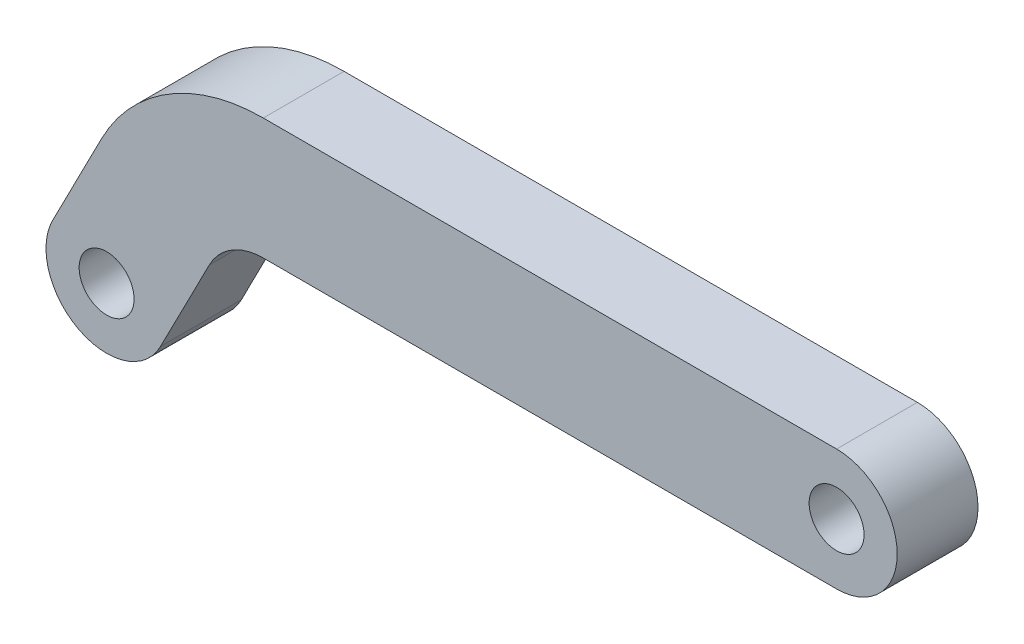
SolidWorks part; units mm, degrees
ref_plane "Front Plane" through (0, 0, 0) normal (0, 0, 1) x (1, 0, 0)
ref_plane "Top Plane" through (0, 0, 0) normal (0, 1, 0) x (1, 0, 0)
ref_plane "Right Plane" through (0, 0, 0) normal (1, 0, 0) x (0, 0, -1)
sketch "Sketch1" plane through (0, 0, 0) normal (0, 0, 1) x (1, 0, 0)
  line L0 (57.3602, 17.4078) -> (12.3107, 17.4078)
  line L2 (57.3602, 7.8828) -> (12.3107, 7.8828)
  line L3 (4.2363, -2.176) -> (8.0744, 5.2963)
  line L4 (-4.2363, 2.176) -> (-0.3983, 9.6482)
  line L5 (0, 0) -> (57.3602, 12.6453) construction
  circle A0 centre (0, 0) radius 2.159
  circle A1 centre (57.3602, 12.6453) radius 2.159
  arc A2 (57.3602, 7.8828) -> (57.3602, 17.4078) centre (57.3602, 12.6453) ccw
  arc A4 (-4.2363, 2.176) -> (4.2363, -2.176) centre (0, 0) ccw
  arc A5 (12.3107, 7.8828) -> (8.0744, 5.2963) centre (12.3107, 3.1203) ccw
  arc A6 (12.3107, 17.4078) -> (-0.3983, 9.6482) centre (12.3107, 3.1203) ccw
  arc A7 (12.4022, 2.7341) -> (12.3107, 3.1203) centre (0, 0) ccw construction
  point P9 (12.4022, 2.7341)
  dimension "D1" = 4.318
  dimension "D4" = 4.7625
  dimension "D5" = 4.7625
  dimension "D6" = 12.7
  dimension "D7" = 4.7625
  dimension "D2" = 58.7375
  dimension "D3" = 0.3969
extrude "Boss-Extrude1" add sketch "Sketch1" along normal mid plane 6.35
